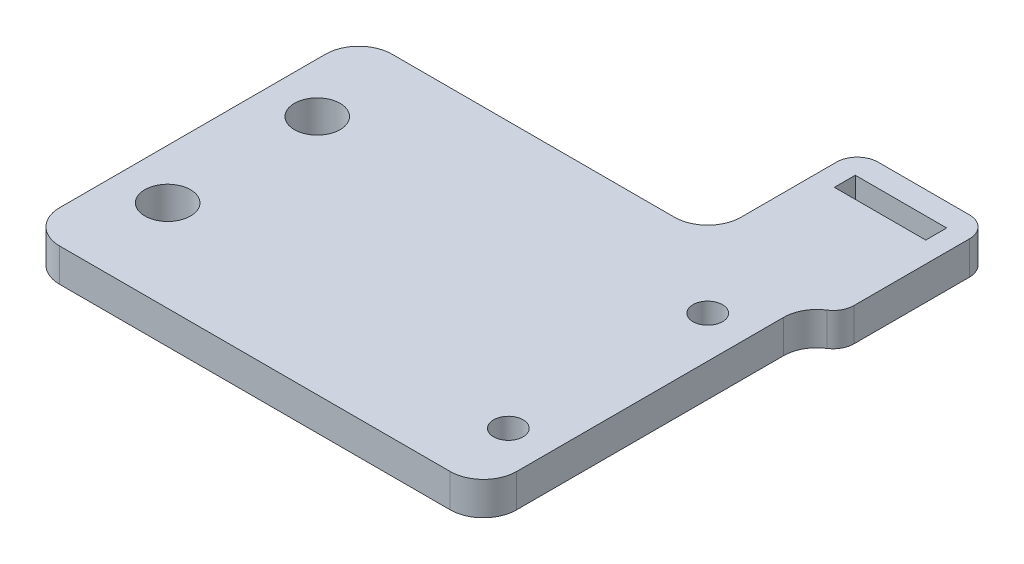
SolidWorks part; units mm, degrees
ref_plane "Front" through (0, 0, 0) normal (0, 0, 1) x (1, 0, 0)
ref_plane "Top" through (0, 0, 0) normal (0, 1, 0) x (1, 0, 0)
ref_plane "Right" through (0, 0, 0) normal (1, 0, 0) x (0, 0, -1)
sketch "Sketch1" plane through (0, 0, 0) normal (0, 1, 0) x (1, 0, 0)
  line L1 (0, 0) -> (34.925, 0)
  line L2 (0, 0) -> (0, 25.4)
  line L3 (0, 25.4) -> (34.925, 25.4)
  line L4 (34.925, 0) -> (34.925, 25.4)
  dimension "D1" = 25.4
  dimension "D2" = 34.925
extrude "Boss-Extrude1" add sketch "Sketch1" along normal blind 2.54
sketch "Sketch2" plane through (0, 2.54, 0) normal (0, 1, 0) x (1, 0, 0)
  line L0 (0, 12.7) -> (34.925, 12.7) construction
  line L1 (0, 25.4) -> (0, 0) construction
  line L2 (34.925, 0) -> (34.925, 25.4) construction
  circle A0 centre (3.81, 18.415) radius 1.7462
  circle A1 centre (3.81, 6.985) radius 1.7463
  dimension "D1" = 3.4925
  dimension "D2" = 5.715
  dimension "D3" = 3.81
extrude "Cut-Extrude3" cut sketch "Sketch2" along normal through all and the other way through all
sketch "Sketch5" plane through (0, 2.54, 0) normal (0, 1, 0) x (1, 0, 0)
  line L0 (0, 12.7) -> (34.925, 12.7) construction
  line L1 (0, 25.4) -> (0, 0) construction
  line L2 (34.925, 0) -> (34.925, 25.4) construction
  line L3 (34.925, 25.4) -> (0, 25.4) construction
  circle A0 centre (31.75, 20.32) radius 1.1303
  circle A1 centre (31.75, 5.08) radius 1.1303
  dimension "D1" = 2.2606
  dimension "D2" = 5.08
  dimension "D3" = 3.175
extrude "Cut-Extrude4" cut sketch "Sketch5" against normal through all
sketch "Sketch6" plane through (0, 2.54, 0) normal (0, 1, 0) x (1, 0, 0)
  line L0 (31.75, 20.32) -> (31.75, 5.08) construction
  line L1 (31.75, 20.32) -> (31.75, 38.7587) construction
  line L2 (34.925, 25.4) -> (0, 25.4) construction
  line L3 (36.83, 36.83) -> (26.67, 36.83)
  line L4 (36.83, 36.83) -> (36.83, 25.4)
  line L5 (36.83, 25.4) -> (26.67, 25.4)
  line L6 (26.67, 36.83) -> (26.67, 25.4)
  line L7 (36.83, 36.83) -> (26.67, 25.4) construction
  line L8 (36.83, 25.4) -> (26.67, 36.83) construction
  point P5 (31.75, 31.115)
  point P12 (31.75, 12.7)
  dimension "D1" = 24.13
  dimension "D2" = 10.16
extrude "Boss-Extrude2" add sketch "Sketch6" against normal blind 2.54
sketch "Sketch7" plane through (0, 2.54, 0) normal (0, 1, 0) x (1, 0, 0)
  line L0 (31.75, 5.08) -> (31.75, 13.0272) construction
  line L1 (31.75, 13.0272) -> (31.75, 36.83) construction
  line L2 (36.83, 36.83) -> (26.67, 36.83) construction
  line L4 (28.2575, 35.0901) -> (35.2425, 35.0901)
  line L5 (28.2575, 35.0901) -> (28.2575, 33.4899)
  line L6 (28.2575, 33.4899) -> (35.2425, 33.4899)
  line L7 (35.2425, 35.0901) -> (35.2425, 33.4899)
  line L8 (28.2575, 35.0901) -> (35.2425, 33.4899) construction
  line L9 (28.2575, 33.4899) -> (35.2425, 35.0901) construction
  point P3 (31.75, 34.29)
  dimension "D1" = 2.54
  dimension "D2" = 1.6002
  dimension "D3" = 6.985
extrude "Cut-Extrude5" cut sketch "Sketch7" against normal through all
fillet "Fillet1" radius 2.54 2 edges at (34.925, 1.27, -25.4) (26.67, 1.27, -25.4)
fillet "Fillet2" radius 1.5875 3 edges at (36.83, 1.27, -36.83) (26.67, 1.27, -36.83) (36.83, 1.27, -25.4)
fillet "Fillet3" radius 2.54 3 edges at (0, 1.27, 0) (0, 1.27, -25.4) (34.925, 1.27, 0)
